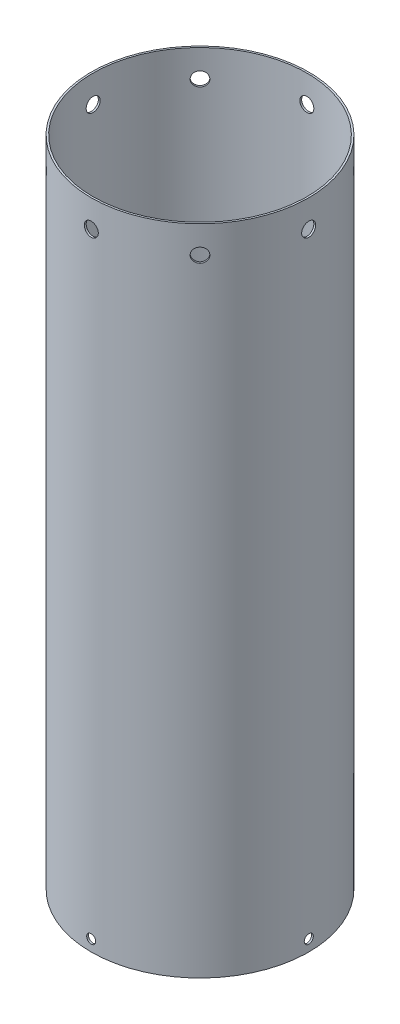
SolidWorks part; units mm, degrees
material "6061-T6 (SS)"
ref_plane "Front Plane" through (0, 0, 0) normal (0, 0, 1) x (1, 0, 0)
ref_plane "Top Plane" through (0, 0, 0) normal (0, 1, 0) x (1, 0, 0)
ref_plane "Right Plane" through (0, 0, 0) normal (1, 0, 0) x (0, 0, -1)
sketch "Sketch1" plane through (0, 0, 0) normal (0, 1, 0) x (1, 0, 0)
  circle A0 centre (0, 0) radius 76.2
  dimension "D1" = 152.4
extrude "Boss-Extrude1" add sketch "Sketch1" along normal blind 457.2
sketch "Sketch2" plane through (0, 457.2, 0) normal (0, 1, 0) x (1, 0, 0)
  circle A0 centre (0, 0) radius 74.93
  dimension "D1" = 149.86
extrude "Cut-Extrude1" cut sketch "Sketch2" against normal through all
sketch "Sketch3" plane through (0, 0, 0) normal (0, 0, 1) x (1, 0, 0)
  line L0 (0, 457.2) -> (0, 438.15)
  line L1 (76.2, 457.2) -> (-76.2, 457.2) construction
  circle A0 centre (0, 438.15) radius 4.8895
  dimension "D1" = 19.05
  dimension "D2" = 9.779
extrude "Cut-Extrude2" cut sketch "Sketch3" against normal through all both and the other way through all contours A0
pattern_circular "CirPattern1" count 8 over 360 about axis through (0, 457.2, 0) along (0, -1, 0) of "Cut-Extrude2"
sketch "Sketch4" plane through (0, 0, 0) normal (0, 0, 1) x (1, 0, 0)
  line L0 (0, 0) -> (0, 7.9375)
  line L1 (-76.2, 0) -> (76.2, 0) construction
  circle A0 centre (0, 7.9375) radius 3.175
extrude "Cut-Extrude3" cut sketch "Sketch4" against normal through all both and the other way through all contours A0
pattern_circular "CirPattern2" count 4 over 360 about axis through (0, 457.2, 0) along (0, -1, 0) of "Cut-Extrude3" reverse direction yes
